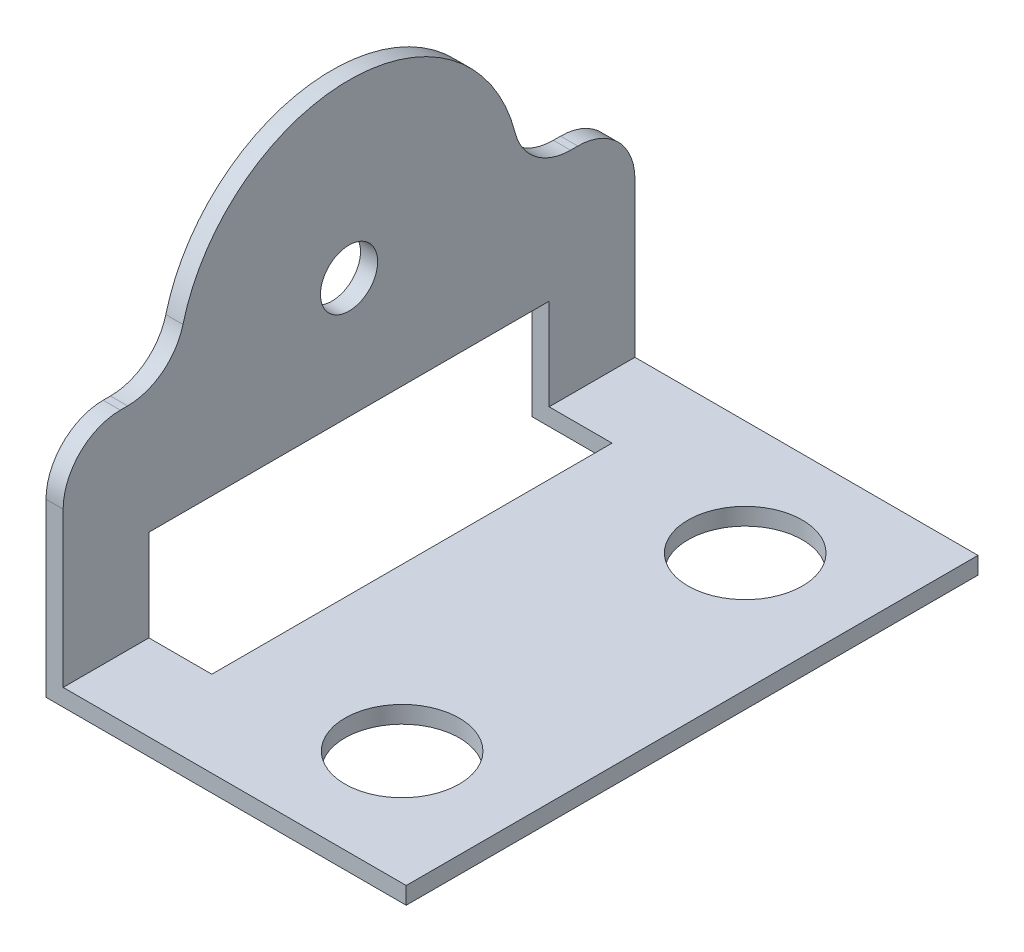
SolidWorks part; units mm, degrees
ref_plane "Front Plane" through (0, 0, 0) normal (0, 0, 1) x (1, 0, 0)
ref_plane "Top Plane" through (0, 0, 0) normal (0, 1, 0) x (1, 0, 0)
ref_plane "Right Plane" through (0, 0, 0) normal (1, 0, 0) x (0, 0, -1)
sketch "Sketch1" plane through (0, 0, 0) normal (1, 0, 0) x (0, 0, -1)
  line L0 (25, 0) -> (15, 0)
  line L1 (25, 0) -> (25, -20)
  line L2 (-25, 0) -> (-25, -20)
  line L3 (25, -20) -> (-25, -20)
  line L4 (-25, -18.5) -> (25, -18.5)
  line L5 (-15, 0) -> (-25, 0)
  line L11 (-17.5, -18.5) -> (17.5, -18.5)
  line L12 (-17.5, -18.5) -> (-17.5, -10.5)
  line L13 (-17.5, -10.5) -> (17.5, -10.5)
  line L14 (17.5, -18.5) -> (17.5, -10.5)
  arc A0 (15, 0) -> (-15, 0) centre (0, 0) ccw
  circle A1 centre (0, 0) radius 2.5
  point P15 (0, -10.5)
  dimension "D1" = 30
  dimension "D4" = 35
  dimension "D2" = 50
  dimension "D3" = 1.5
  dimension "10" = 20
  dimension "D5" = 8
extrude "Boss-Extrude1" add sketch "Sketch1" against normal blind 1.5 contours L0 A0 L5 L2 L4 L1 A1 | L4 L2 L3 L1 region at (0, -9.25, -24.3981) region at (0, -19.25, 0)
extrude "Boss-Extrude2" add sketch "Sketch1<3>" along normal blind 30 contours L4 L2 L3 L1 region at (0, -19.25, 0)
sketch "Sketch1<3>" plane through (0, 0, 0) normal (1, 0, 0) x (0, 0, -1) same geometry as "Sketch1"
fillet "Fillet1" radius 5 4 edges at (-0.75, 0, -15) (-0.75, 0, 15) (-0.75, 0, -25) (-0.75, 0, 25)
sketch "Sketch2" plane through (0, -18.5, 0) normal (0, 1, 0) x (1, 0, 0)
  line L1 (-1.5, -17.5) -> (5.5, -17.5)
  line L2 (-1.5, -17.5) -> (-1.5, 17.5)
  line L3 (-1.5, 17.5) -> (5.5, 17.5)
  line L4 (5.5, -17.5) -> (5.5, 17.5)
  circle A0 centre (19.6423, 15) radius 5
  circle A1 centre (19.6423, -15) radius 5
  point P9 (0, 0)
  dimension "D2" = 10
  dimension "D1" = 7
  dimension "D3" = 30
  dimension "D4" = 15
extrude "Cut-Extrude1" cut sketch "Sketch2" against normal blind 30 contours L4 L3 L2 L1 | A1 | A0
